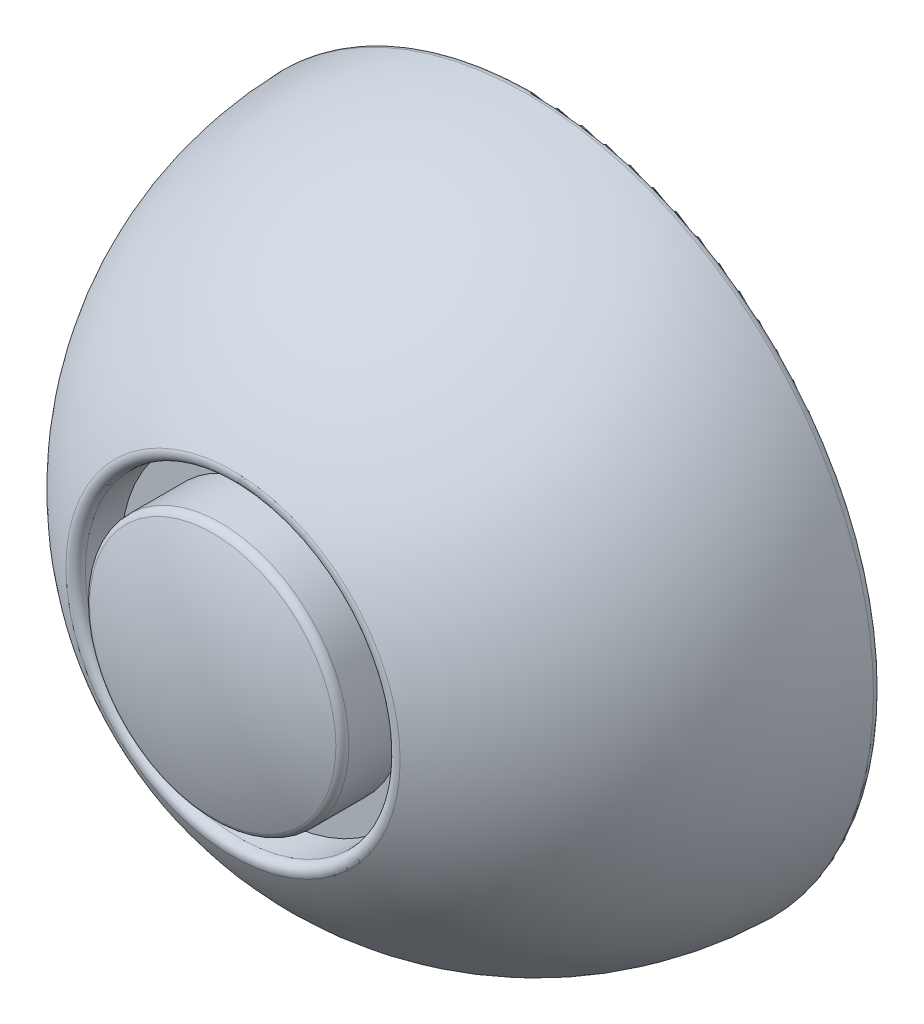
SolidWorks part; units mm, degrees
ref_plane "Front Plane" through (0, 0, 0) normal (0, 0, 1) x (1, 0, 0)
ref_plane "Top Plane" through (0, 0, 0) normal (0, 1, 0) x (1, 0, 0)
ref_plane "Right Plane" through (0, 0, 0) normal (1, 0, 0) x (0, 0, -1)
ref_axis "Polar Axis" through (0, 0, -14.3) along (0, 0, 1)
ref_axis "Solar Axis" through (-14.3, 0, 0) along (1, 0, 0)
sketch "Sketch2" plane through (0, 0, 0) normal (0, 1, 0) x (1, 0, 0)
  line L9 (0, 0) -> (-3.8609, 0) construction
  line L11 (4.7, -8.8267) -> (4.7, -9.3894) construction
  line L12 (0, 0) -> (0, -12.0023) construction
  line L13 (6.8458, -7.2894) -> (1.6, -7.2894)
  line L14 (1.6, -7.2894) -> (1.6, -8.2894)
  line L15 (3.9, -7.8894) -> (3.9, -9.7488)
  line L16 (4.7, -7.8894) -> (3.9, -7.8894)
  line L17 (4.7, -9.3894) -> (4.7, -7.8894)
  line L18 (1.6, -8.2894) -> (0, -9.5)
  line L19 (0, -10.5) -> (0, -9.5)
  line L20 (10, 0) -> (10.5, 0)
  arc A0 (0, -10.5) -> (3.9, -9.7488) centre (0, 0) ccw
  arc A1 (4.7, -9.3894) -> (10.5, 0) centre (0, 0) ccw
  arc A4 (10, 0) -> (6.8458, -7.2894) centre (0, 0) cw
  dimension "D1" = 21
  dimension "D2" = 0.5
revolve "Main Body" add sketch "Sketch2" angle 360 about L12
fillet "Fillet1" radius 0.25 5 edges at (-10.5, 0, 0) (-10, 0, 0) (-3.9, 0, 9.7488) (-4.7, 0, 9.3894) (-1.6, 0, 7.2894)
